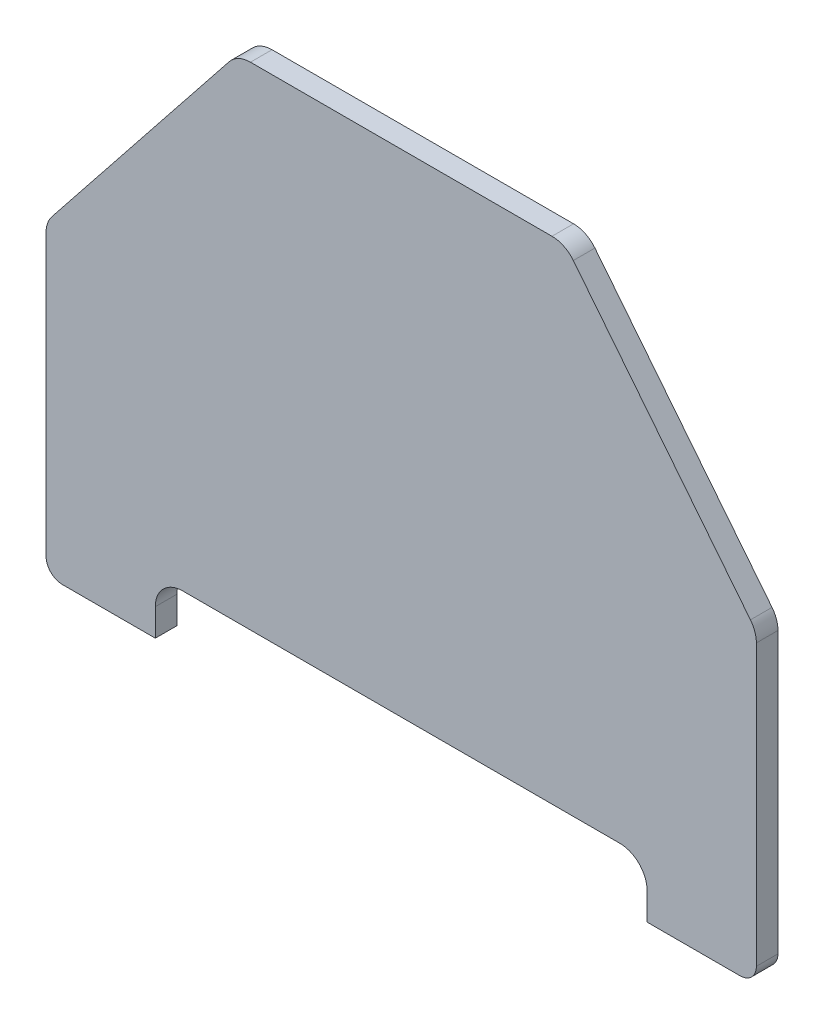
SolidWorks part; units mm, degrees
ref_plane "Front Plane" through (0, 0, 0) normal (0, 0, 1) x (1, 0, 0)
ref_plane "Top Plane" through (0, 0, 0) normal (0, 1, 0) x (1, 0, 0)
ref_plane "Right Plane" through (0, 0, 0) normal (1, 0, 0) x (0, 0, -1)
sketch "Sketch1" plane through (0, 0, 0) normal (0, 0, 1) x (1, 0, 0)
  line L0 (0, 56) -> (35, 100)
  line L2 (0, 56) -> (0, 0)
  line L3 (0, 0) -> (20, 0)
  line L4 (130, 56) -> (130, 0)
  line L8 (20, 0) -> (20, 10)
  line L9 (20, 10) -> (110, 10)
  line L10 (110, 0) -> (110, 10)
  line L11 (35, 100) -> (95, 100)
  line L12 (95, 100) -> (130, 56)
  line L13 (110, 0) -> (130, 0)
  point P0 (0, 0)
  dimension "D1" = 130
  dimension "D2" = 20
  dimension "D3" = 56
  dimension "D4" = 60
  dimension "D5" = 10
  dimension "D6" = 100
extrude "Boss-Extrude2" add sketch "Sketch1" along normal blind 3.95
fillet "Fillet1" radius 5 6 edges at (130, 56, 1.975) (95, 100, 1.975) (35, 100, 1.975) (0, 56, 1.975) (110, 10, 1.975) (20, 10, 1.975)
fillet "Fillet2" radius 3 2 edges at (130, 0, 1.975) (0, 0, 1.975)
